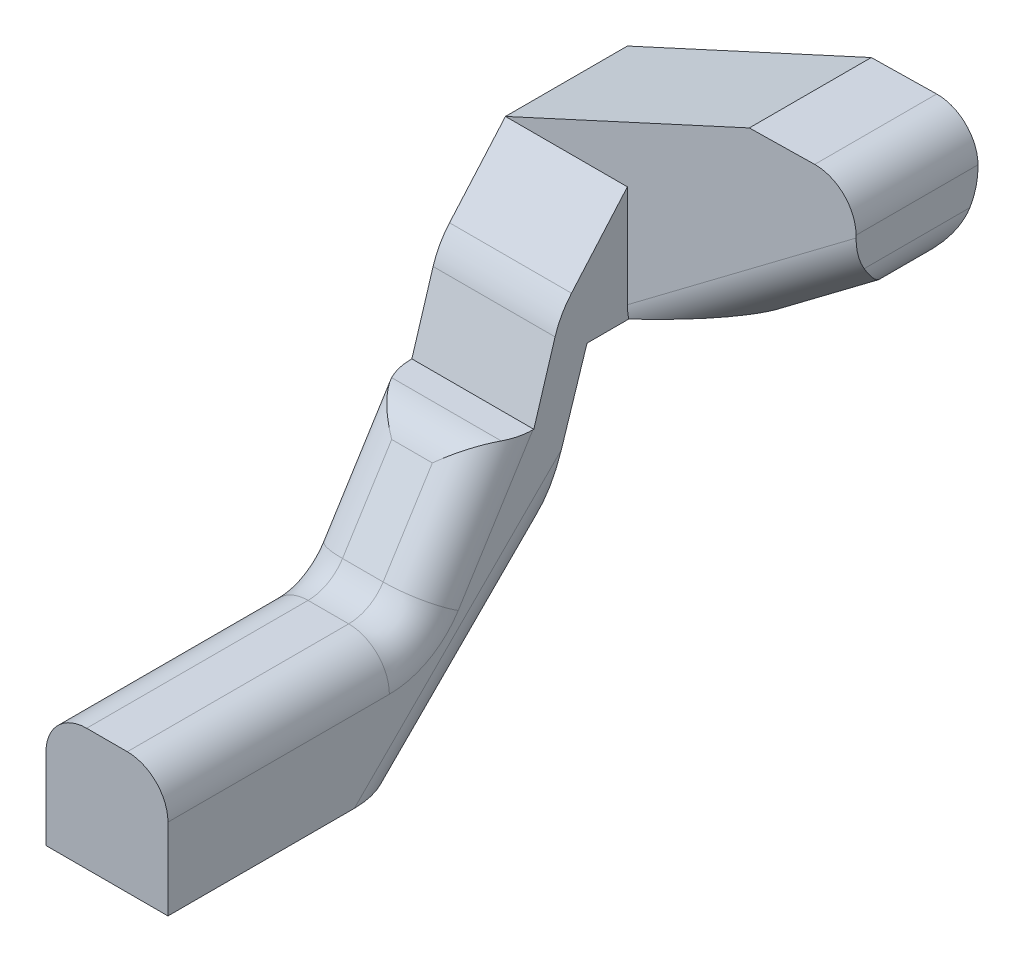
SolidWorks part; units mm, degrees
ref_plane "Front Plane" through (0, 0, 0) normal (0, 0, 1) x (1, 0, 0)
ref_plane "Top Plane" through (0, 0, 0) normal (0, 1, 0) x (1, 0, 0)
ref_plane "Right Plane" through (0, 0, 0) normal (1, 0, 0) x (0, 0, -1)
sketch "Sketch1" plane through (0, 0, 0) normal (0, 0, 1) x (1, 0, 0)
  line L1 (7.5, 7.5) -> (-7.5, 7.5)
  line L2 (7.5, 7.5) -> (7.5, -7.5)
  line L3 (7.5, -7.5) -> (-7.5, -7.5)
  line L4 (-7.5, 7.5) -> (-7.5, -7.5)
  line L5 (7.5, 7.5) -> (-7.5, -7.5) construction
  line L6 (7.5, -7.5) -> (-7.5, 7.5) construction
  point P0 (0, 0)
  dimension "D1" = 15
  dimension "D2" = 15
extrude "Boss-Extrude1" add sketch "Sketch1" along normal blind 30
sketch "Sketch2" plane through (7.5, 0, 0) normal (1, 0, 0) x (0, 0, -1)
  line L0 (0, 7.5) -> (0, -7.5)
  line L2 (15, 7.5) -> (0, -7.5)
  line L3 (0, 7.5) -> (8.9884, 21.8448)
  line L4 (8.9884, 21.8448) -> (15, 21.8448)
  line L5 (15, 21.8448) -> (18.2361, 32.4148)
  line L7 (26.5103, 32.4148) -> (26.5103, 27.7422)
  line L8 (26.5103, 27.7422) -> (21.5458, 27.7422)
  line L9 (21.5458, 27.7422) -> (15, 7.5)
  line L10 (18.2361, 32.4148) -> (26.5103, 41.9129)
  line L11 (26.5103, 41.9129) -> (26.5103, 32.4148)
  dimension "D1" = 15
extrude "Boss-Extrude2" add sketch "Sketch2" against normal up to surface (15 mm away) up to face at (-7.5, 0, 15)
sketch "Sketch3" plane through (0, 0, -26.5103) normal (0, 0, -1) x (-1, 0, 0)
  line L0 (-7.5, 27.7422) -> (-22.4951, 34.3821)
  line L1 (7.5, 27.7422) -> (-7.5, 27.7422)
  line L2 (7.5, 27.7422) -> (7.5, 41.9129)
  line L6 (-22.4951, 55.6857) -> (7.5, 41.9129)
  line L7 (-22.4951, 34.3821) -> (-35.6228, 44.262)
  line L8 (-35.6228, 44.262) -> (-35.6228, 55.9084)
  line L11 (-22.4951, 55.6857) -> (-35.6228, 55.9084)
extrude "Boss-Extrude3" add sketch "Sketch3" along normal blind 15
fillet "Fillet1" radius 5 1 edges at (35.6228, 55.9084, -34.0103)
fillet "Fillet2" radius 5 4 edges at (29.059, 39.3221, -41.5103) (22.4951, 34.3821, -34.0103) (29.059, 39.3221, -26.5103) (35.6228, 44.262, -34.0103)
fillet "Fillet3" radius 5 4 edges at (0, -7.5, 0) (7.5, 0, -7.5) (0, 7.5, -15) (-7.5, 0, -7.5)
fillet "Fillet4" radius 5 6 edges at (7.5, 7.5, 15) (-7.5, 7.5, 15) (0, 21.8448, -8.9884) (7.5, 14.6724, -4.4942) (0, 7.5, 0) (-7.5, 14.6724, -4.4942)
fillet "Fillet5" radius 10 1 edges at (0, 32.4148, -18.2361)
